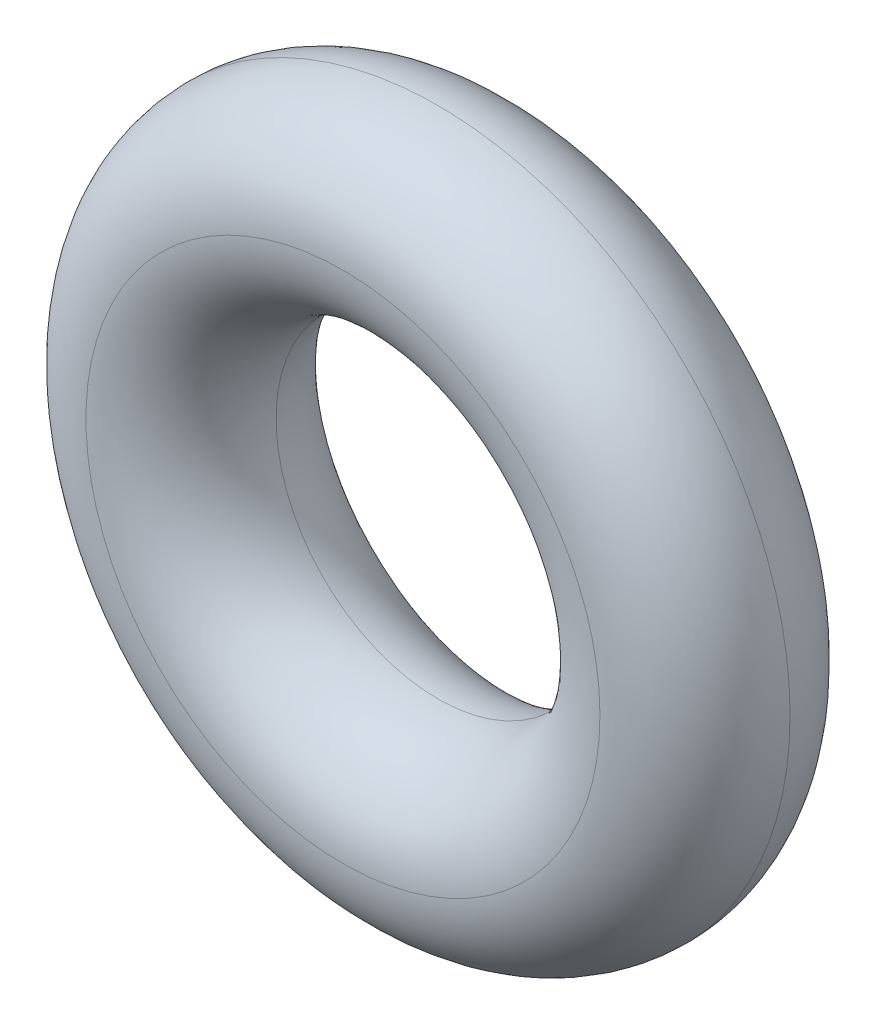
SolidWorks part; units mm, degrees
ref_plane "前视基准面" through (0, 0, 0) normal (0, 0, 1) x (1, 0, 0)
ref_plane "上视基准面" through (0, 0, 0) normal (0, 1, 0) x (1, 0, 0)
ref_plane "右视基准面" through (0, 0, 0) normal (1, 0, 0) x (0, 0, -1)
sketch "草图1" plane through (0, 0, 0) normal (0, 0, 1) x (1, 0, 0)
  circle A2 centre (0, 0) radius 115
  circle A3 centre (0, 0) radius 250
  dimension "D1" = 500
  dimension "D3" = 230
extrude "凸台-拉伸1" add sketch "草图1" along normal blind 135
fillet "圆角1" radius 67.5 4 edges at (115, 0, 0) (250, 0, 0) (250, 0, 135) (115, 0, 135)
